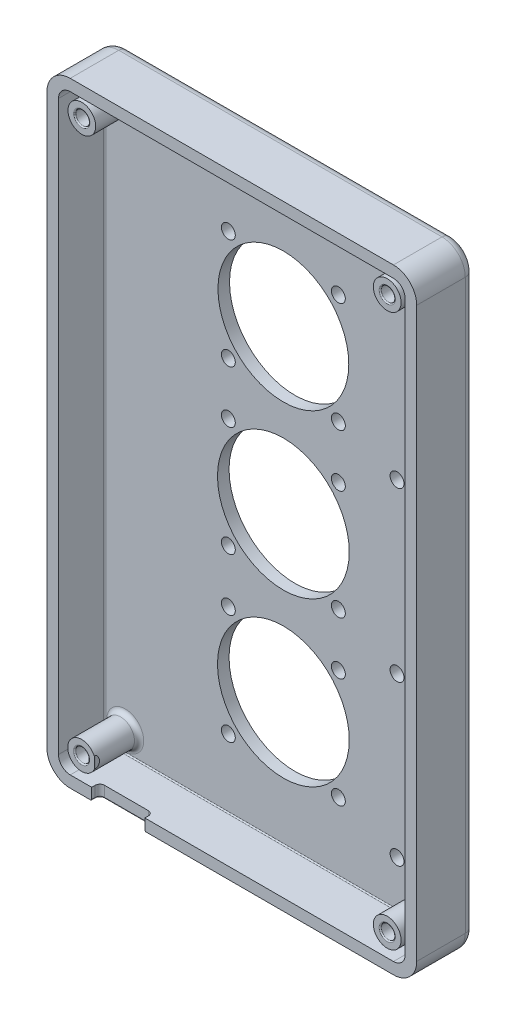
SolidWorks part; units mm, degrees
material "Plastique personnalisé"
ref_plane "Plan de face" through (0, 0, 0) normal (0, 0, 1) x (1, 0, 0)
ref_plane "Plan de dessus" through (0, 0, 0) normal (0, 1, 0) x (1, 0, 0)
ref_plane "Plan de droite" through (0, 0, 0) normal (1, 0, 0) x (0, 0, -1)
sketch "Esquisse1" plane through (0, 0, 0) normal (0, 0, 1) x (1, 0, 0)
  line L1 (-34.96, -64) -> (34.96, -64)
  line L2 (-37.5, -61.46) -> (-37.5, 61.46)
  line L3 (-34.96, 64) -> (34.96, 64)
  line L4 (37.5, -61.46) -> (37.5, 61.46)
  line L5 (-37.5, -64) -> (37.5, 64) construction
  line L6 (-37.5, 64) -> (37.5, -64) construction
  arc A0 (34.96, -64) -> (37.5, -61.46) centre (34.96, -61.46) ccw
  arc A1 (-34.96, -64) -> (-37.5, -61.46) centre (-34.96, -61.46) cw
  arc A2 (-37.5, 61.46) -> (-34.96, 64) centre (-34.96, 61.46) cw
  arc A3 (34.96, 64) -> (37.5, 61.46) centre (34.96, 61.46) cw
  point P0 (0, 0)
  dimension "D3" = 2.54
  dimension "D1" = 128
  dimension "D2" = 75
extrude "Boss.-Extru.1" add sketch "Esquisse1" along normal blind 10
shell "Coque1" thickness 2.5 removed face at (0, 0, 10) outward yes
fillet "Congé1" radius 2 8 edges at (40, 0, -2.5) (38.5238, -65.0238, -2.5) (0, -66.5, -2.5) (-38.5238, -65.0238, -2.5) (-40, 0, -2.5) (-38.5238, 65.0238, -2.5) (0, 66.5, -2.5) (38.5238, 65.0238, -2.5)
sketch "Esquisse3" plane through (0, 0, 0) normal (0, 0, 1) x (1, 0, 0)
  circle A0 centre (-33.02, 59.69) radius 1.5
  circle A1 centre (-33.02, 59.69) radius 3
  circle A2 centre (33.0465, 59.69) radius 1.5
  circle A3 centre (33.0465, 59.69) radius 3
  circle A4 centre (-33.06, -59.69) radius 3
  circle A5 centre (-33.06, -59.69) radius 1.5
  circle A6 centre (33.0465, -59.759) radius 3
  circle A7 centre (33.0465, -59.759) radius 1.5
  dimension "D1" = 3
  dimension "D2" = 3
extrude "Boss.-Extru.2" add sketch "Esquisse3" along normal up to surface (9.43 mm away)
sketch "Esquisse4" plane through (0, 0, 10) normal (0, 0, 1) x (1, 0, 0)
  line L0 (-24.5364, -63.3046) -> (-24.5364, -64) construction
  line L1 (-34.96, -64) -> (34.96, -64) construction
  line L2 (-24.5364, -64) -> (-24.5364, -64.0598) construction
  line L3 (-24.5364, -64.0598) -> (-24.5364, -66.5) construction
  line L4 (-34.96, -66.5) -> (34.96, -66.5) construction
  line L6 (-29.52, -66.5598) -> (-19.5528, -66.5598)
  line L7 (-29.52, -66.5598) -> (-29.52, -64)
  line L8 (-29.52, -64) -> (-19.5528, -64)
  line L9 (-19.5528, -66.5598) -> (-19.5528, -64)
  line L10 (-29.52, -66.5598) -> (-19.5528, -64) construction
  line L11 (-29.52, -64) -> (-19.5528, -66.5598) construction
  point P5 (-24.5364, -65.2799)
extrude "Enlèv. mat.-Extru.2" cut sketch "Esquisse4" against normal blind 1
fillet "Congé4" radius 1 2 edges at (-19.5528, -65.25, 9) (-29.52, -65.25, 9)
sketch "Esquisse5" plane through (0, 0, -2.5) normal (0, 0, -1) x (-1, 0, 0)
  circle A0 centre (-13.049, 44.9581) radius 1.5
  circle A1 centre (10.751, 44.9581) radius 1.5
  circle A2 centre (10.751, 21.1581) radius 1.5
  circle A3 centre (-13.049, 21.1581) radius 1.5
  circle A4 centre (-13.049, 9.7959) radius 1.5
  circle A5 centre (10.751, 9.8247) radius 1.5
  circle A6 centre (10.751, -13.9753) radius 1.5
  circle A7 centre (-13.049, -13.9753) radius 1.5
  circle A8 centre (-13.049, -25.3963) radius 1.5
  circle A9 centre (10.751, -25.3963) radius 1.5
  circle A10 centre (10.751, -49.1963) radius 1.5
  circle A11 centre (-13.049, -49.1963) radius 1.5
  circle A12 centre (-1.149, -37.2963) radius 14.25
  circle A13 centre (-1.149, -2.0753) radius 14.25
  circle A14 centre (-1.149, 33.0581) radius 14.15
  dimension "D1" = 3
  dimension "D2" = 3
  dimension "D3" = 3
  dimension "D4" = 3
  dimension "D5" = 3
  dimension "D6" = 3
  dimension "D7" = 3
  dimension "D8" = 3
  dimension "D9" = 3
  dimension "D10" = 3
  dimension "D11" = 3
  dimension "D12" = 3
extrude "Enlèv. mat.-Extru.3" cut sketch "Esquisse5" against normal blind 10
sketch "Esquisse6" plane through (0, 0, 0) normal (0, 0, 1) x (1, 0, 0)
  circle A0 centre (25.7401, 16.6531) radius 1.5
  circle A1 centre (25.7401, -19.683) radius 1.5
  circle A2 centre (25.7401, -54.1208) radius 1.5
extrude "Enlèv. mat.-Extru.4" cut sketch "Esquisse6" against normal blind 10
sketch "Esquisse7" plane through (0, -66.5, 0) normal (0, -1, 0) x (1, 0, 0)
  line L0 (-29.52, 10) -> (-19.5528, 10) construction
  line L1 (-24.5668, 10) -> (-24.5668, 8.25) construction
  line L3 (-29.3168, 8.2408) -> (-19.8168, 8.2408)
  line L4 (-30.3168, 9.2408) -> (-30.3168, 10.0092)
  line L5 (-30.3168, 10.0092) -> (-18.8168, 10.0092)
  line L6 (-18.8168, 9.2408) -> (-18.8168, 10.0092)
  line L7 (-30.3168, 8.2408) -> (-18.8168, 10.0092) construction
  line L8 (-30.3168, 10.0092) -> (-18.8168, 8.2408) construction
  arc A0 (-29.3168, 8.2408) -> (-30.3168, 9.2408) centre (-29.3168, 9.2408) cw
  arc A1 (-18.8168, 9.2408) -> (-19.8168, 8.2408) centre (-19.8168, 9.2408) cw
  point P6 (-24.5668, 9.125)
  dimension "D2" = 1
  dimension "D1" = 1.75
  dimension "D3" = 11.5
extrude "Enlèv. mat.-Extru.5" cut sketch "Esquisse7" against normal blind 10
fillet "Congé5" radius 1 4 edges at (-30.06, -59.69, 0) (36.0465, -59.759, 0) (36.0465, 59.69, 0) (-30.02, 59.69, 0)
fillet "Congé6" radius 0.25 8 edges at (36.7561, -63.2561, 0) (0, -64, 0) (-36.7561, -63.2561, 0) (-37.5, 0, 0) (-36.7561, 63.2561, 0) (0, 64, 0) (36.7561, 63.2561, 0) (37.5, 0, 0)
fillet "Congé7" radius 0.25 4 edges at (-34.52, 59.69, 9.43) (-34.56, -59.69, 9.43) (31.5465, -59.759, 9.43) (31.5465, 59.69, 9.43)
fillet "Congé8" radius 0.25 12 edges at (-12.251, -49.1963, -2.5) (11.549, -49.1963, -2.5) (11.549, -25.3963, -2.5) (-12.251, -25.3963, -2.5) (-12.251, -13.9753, -2.5) (11.549, -13.9753, -2.5) (-12.251, 9.8247, -2.5) (11.549, 9.7959, -2.5) (11.549, 21.1581, -2.5) (-12.251, 21.1581, -2.5) (-12.251, 44.9581, -2.5) (11.549, 44.9581, -2.5)
fillet "Congé9" radius 0.25 3 edges at (27.2401, -54.1208, -2.5) (27.2401, -19.683, -2.5) (27.2401, 16.6531, -2.5)
fillet "Congé10" radius 0.25 5 edges at (-30.3168, -66.5, 9.6204) (-18.8168, -66.5, 9.6204) (-19.1097, -66.5, 8.5337) (-24.5668, -66.5, 8.2408) (-30.0239, -66.5, 8.5337)
